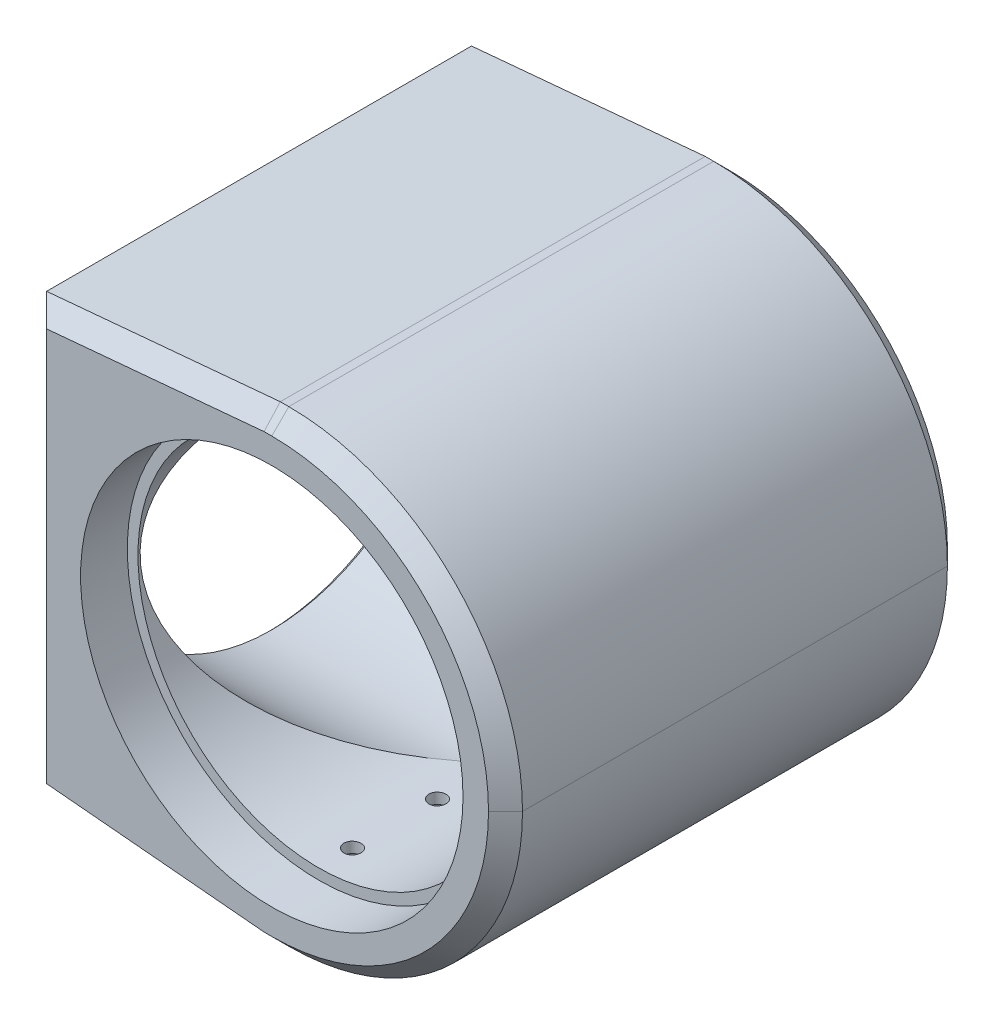
SolidWorks part; units mm, degrees
ref_plane "前视基准面" through (0, 0, 0) normal (0, 0, 1) x (1, 0, 0)
ref_plane "上视基准面" through (0, 0, 0) normal (0, 1, 0) x (1, 0, 0)
ref_plane "右视基准面" through (0, 0, 0) normal (1, 0, 0) x (0, 0, -1)
sketch "草图1" plane through (0, 0, 0) normal (0, 0, 1) x (1, 0, 0)
  line L1 (0, 0) -> (112, 0)
  line L2 (0, 0) -> (0, -110)
  line L3 (0, -110) -> (112, -110)
  line L4 (112, 0) -> (112, -110)
  dimension "D1" = 110
  dimension "D2" = 112
extrude "拉伸1" add sketch "草图1" along normal blind 126
fillet "圆角1" radius 55 2 edges at (112, -110, 63) (112, 0, 63)
sketch "草图9" plane through (0, 0, 126) normal (0, 0, 1) x (1, 0, 0)
  circle A0 centre (57, -55) radius 42.5
  dimension "D1" = 85
extrude "切除-拉伸5" cut sketch "草图9" against normal blind 104
sketch "草图10" plane through (0, 0, 0) normal (-1, 0, 0) x (0, 0, 1)
  circle A0 centre (63, -55) radius 42.5
  dimension "D1" = 85
extrude "切除-拉伸6" cut sketch "草图10" against normal blind 57
sketch "草图11" plane through (0, 0, 0) normal (0, 0, -1) x (-1, 0, 0)
  circle A0 centre (-57, -55) radius 42.5
  dimension "D1" = 85
extrude "切除-拉伸7" cut sketch "草图11" against normal blind 50
chamfer "倒角1" distance 55 distance2 5 1 edges at (0, 0, 63) first distance on face at (28.5, 0, 63)
chamfer "倒角2" distance 5 distance2 55 1 edges at (0, -110, 63) first distance on face at (0, -97.5, 63)
sketch "草图14" plane through (0, 0, 0) normal (0, 1, 0) x (1, 0, 0)
  line L1 (129.8618, 0) -> (-13.2276, 0)
  line L2 (129.8618, 0) -> (129.8618, -9)
  line L3 (129.8618, -9) -> (-13.2276, -9)
  line L4 (-13.2276, 0) -> (-13.2276, -9)
  line L6 (-13.2276, -126) -> (-13.2276, -117)
  line L7 (129.8618, -117) -> (-13.2276, -117)
  line L8 (129.8618, -126) -> (129.8618, -117)
  line L9 (129.8618, -126) -> (-13.2276, -126)
  dimension "D1" = 9
  dimension "D2" = 9
extrude "切除-拉伸8" cut sketch "草图14" against normal through all
chamfer "倒角5" distance 4 distance2 4 1 edges at (0, -55, 117)
chamfer "倒角6" distance 4 distance2 4 1 edges at (0, -55, 9)
sketch "草图17" plane through (0, 0, 0) normal (-1, 0, 0) x (0, 0, 1)
  circle A0 centre (63, -55) radius 47.5
  circle A1 centre (63, -55) radius 42.5
sketch "草图18" plane through (0, 0, 0) normal (-1, 0, 0) x (0, 0, 1)
  circle A2 centre (23, -15) radius 5
  circle A3 centre (103, -15) radius 5
  circle A4 centre (23, -95) radius 5
  circle A5 centre (103, -95) radius 5
extrude "切除-拉伸9" cut sketch "草图18" against normal blind 21
sketch "草图19" plane through (0, 0, 117) normal (0, 0, 1) x (1, 0, 0)
  circle A0 centre (57, -55) radius 45
extrude "切除-拉伸10" cut sketch "草图19" against normal blind 11
sketch "草图20" plane through (0, 0, 9) normal (0, 0, -1) x (-1, 0, 0)
  circle A0 centre (-57, -55) radius 45
extrude "切除-拉伸11" cut sketch "草图20" against normal blind 11
chamfer "倒角7" distance 4 angle 45 12 edges at (29.5, -107.6818, 117) (29.5, -2.3182, 117) (56, -110, 117) (95.8909, -93.8909, 117) (56, 0, 117) (95.8909, -16.1091, 117) (29.5, -107.6818, 9) (29.5, -2.3182, 9) (56, 0, 9) (95.8909, -16.1091, 9) (56, -110, 9) (95.8909, -93.8909, 9)
extrude "切除-拉伸12" cut sketch "草图17" against normal blind 2
chamfer "倒角8" distance 1 angle 45 1 edges at (2, -97.5, 63)
sketch "草图21" plane through (0, -110, 0) normal (0, -1, 0) x (1, 0, 0)
  line L0 (55, 113) -> (0, 113) construction
  line L1 (55, 113) -> (55, 13) construction
  circle A0 centre (57, 98) radius 5
  circle A1 centre (57, 78) radius 5
  dimension "D2" = 10
  dimension "D1" = 15
  dimension "D3" = 2
  dimension "D4" = 2
extrude "切除-拉伸13" cut sketch "草图21" against normal blind 10
sketch "草图22" plane through (0, -100, 0) normal (0, -1, 0) x (1, 0, 0)
  circle A0 centre (57, 78) radius 2
  circle A1 centre (57, 98) radius 2
extrude "切除-拉伸14" cut sketch "草图22" against normal blind 10
